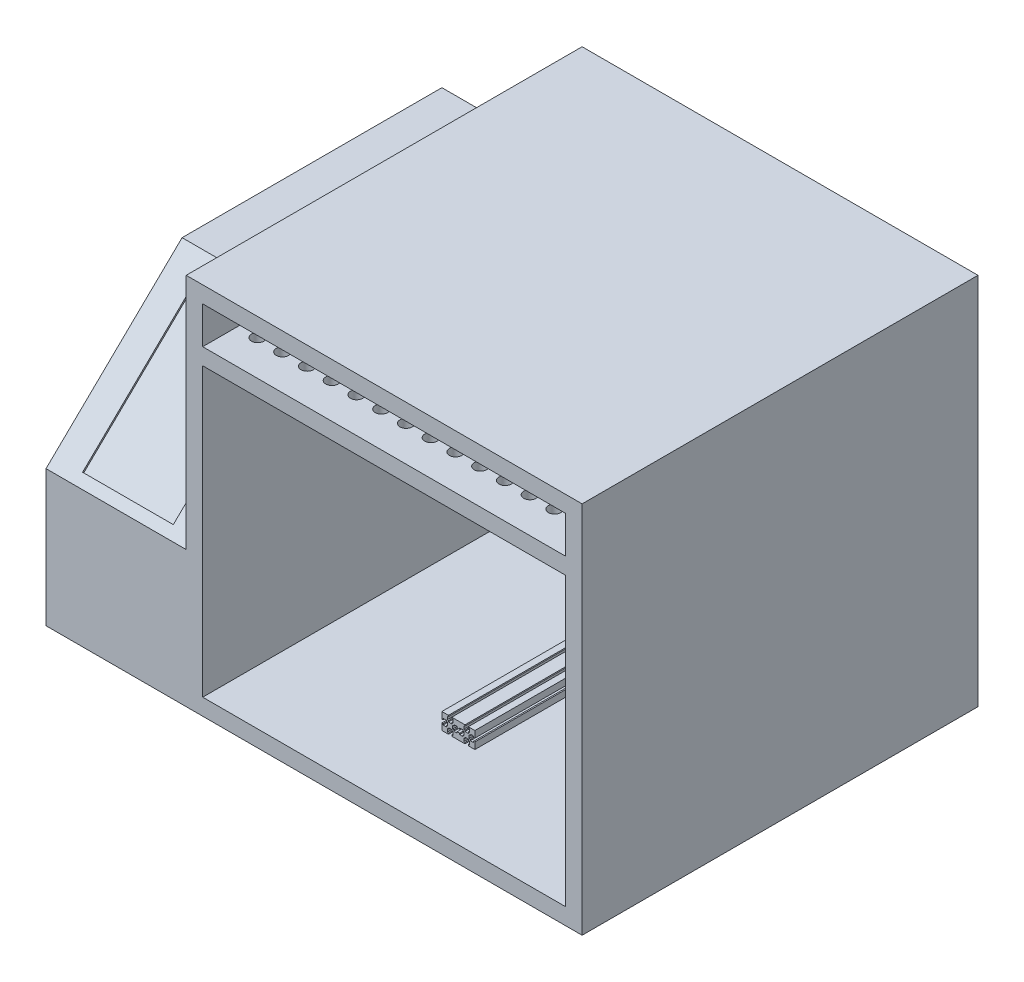
SolidWorks part; units mm, degrees
ref_plane "前视基准面" through (0, 0, 0) normal (0, 0, 1) x (1, 0, 0)
ref_plane "上视基准面" through (0, 0, 0) normal (0, 1, 0) x (1, 0, 0)
ref_plane "右视基准面" through (0, 0, 0) normal (1, 0, 0) x (0, 0, -1)
other "Configuration Table"
sketch "草图1" plane through (0, 0, 0) normal (0, 0, 1) x (1, 0, 0)
  line L0 (170, 20) -> (170, 305)
  line L1 (0, 0) -> (650, 0)
  line L2 (0, 0) -> (0, 325)
  line L3 (170, 453) -> (650, 453)
  line L4 (650, 0) -> (650, 453)
  line L5 (170, 453) -> (170, 325)
  line L6 (190, 388) -> (630, 388)
  line L7 (0, 325) -> (170, 325)
  line L8 (190, 20) -> (190, 368)
  line L9 (630, 20) -> (630, 368)
  line L10 (190, 368) -> (630, 368)
  line L11 (190, 20) -> (630, 20)
  line L12 (170, 20) -> (20, 20)
  line L13 (20, 20) -> (20, 305)
  line L14 (20, 305) -> (170, 305)
  line L15 (190, 388) -> (190, 433)
  line L16 (630, 388) -> (630, 433)
  line L17 (190, 433) -> (630, 433)
  line L18 (170, 325) -> (170, 453)
  line L19 (170, 305) -> (170, 20)
  point P12 (0, 0)
  point P17 (0, 0)
  point P18 (0, 0)
  dimension "D1" = 650
  dimension "D2" = 65
  dimension "D3" = 20
  dimension "D4" = 20
  dimension "D5" = 325
  dimension "D7" = 20
  dimension "D8" = 20
  dimension "D9" = 20
  dimension "D10" = 453
  dimension "D11" = 20
  dimension "D12" = 20
extrude "凸台-拉伸1" add sketch "草图1" along normal blind 480 contours L7 L2 L1 L4 L3 L5 L11 L8 L10 L9 L13 L14 L0 L12 L15 L17 L16 L6 region at (7.9228, 162.5, 0)
sketch "草图2" plane through (0, 0, 0) normal (0, 0, -1) x (-1, 0, 0)
  line L0 (0, 0) -> (-650, 0) construction
  line L1 (-650, 453) -> (-170, 453)
  line L2 (-650, 453) -> (-650, 0)
  line L3 (-650, 0) -> (-170, 0)
  line L4 (-170, 453) -> (-170, 325)
  line L6 (0, 325) -> (-170, 325)
  line L7 (0, 325) -> (0, 0)
  line L8 (0, 0) -> (-170, 0)
extrude "凸台-拉伸2" add sketch "草图2" against normal blind 20
sketch "草图3" plane through (0, 368, 0) normal (0, -1, 0) x (1, 0, 0)
  line L0 (630, 480) -> (630, 0)
  line L1 (0, 0) -> (650, 0) construction
  line L2 (190, 480) -> (190, 0)
  line L3 (0, 480) -> (650, 480) construction
  line L4 (190, 460) -> (650, 460)
  line L5 (650, 480) -> (650, 0) construction
  line L6 (190, 20) -> (650, 20)
  circle A0 centre (213.812, 437.12) radius 7.5
  circle A1 centre (213.812, 407.12) radius 7.5
  circle A2 centre (213.812, 377.12) radius 7.5
  circle A3 centre (213.812, 347.12) radius 7.5
  circle A4 centre (213.812, 317.12) radius 7.5
  circle A5 centre (213.812, 287.12) radius 7.5
  circle A6 centre (213.812, 257.12) radius 7.5
  circle A7 centre (213.812, 227.12) radius 7.5
  circle A8 centre (213.812, 197.12) radius 7.5
  circle A9 centre (213.812, 167.12) radius 7.5
  circle A10 centre (213.812, 137.12) radius 7.5
  circle A11 centre (213.812, 107.12) radius 7.5
  circle A12 centre (213.812, 77.12) radius 7.5
  circle A13 centre (213.812, 47.12) radius 7.5
  circle A14 centre (243.812, 407.12) radius 7.5
  circle A15 centre (243.812, 377.12) radius 7.5
  circle A16 centre (243.812, 347.12) radius 7.5
  circle A17 centre (243.812, 317.12) radius 7.5
  circle A18 centre (243.812, 287.12) radius 7.5
  circle A19 centre (243.812, 257.12) radius 7.5
  circle A20 centre (243.812, 227.12) radius 7.5
  circle A21 centre (243.812, 197.12) radius 7.5
  circle A22 centre (243.812, 167.12) radius 7.5
  circle A23 centre (243.812, 137.12) radius 7.5
  circle A24 centre (243.812, 107.12) radius 7.5
  circle A25 centre (243.812, 77.12) radius 7.5
  circle A26 centre (243.812, 47.12) radius 7.5
  circle A27 centre (273.812, 407.12) radius 7.5
  circle A28 centre (273.812, 377.12) radius 7.5
  circle A29 centre (273.812, 347.12) radius 7.5
  circle A30 centre (273.812, 317.12) radius 7.5
  circle A31 centre (273.812, 287.12) radius 7.5
  circle A32 centre (273.812, 257.12) radius 7.5
  circle A33 centre (273.812, 227.12) radius 7.5
  circle A34 centre (273.812, 197.12) radius 7.5
  circle A35 centre (273.812, 167.12) radius 7.5
  circle A36 centre (273.812, 137.12) radius 7.5
  circle A37 centre (273.812, 107.12) radius 7.5
  circle A38 centre (273.812, 77.12) radius 7.5
  circle A39 centre (273.812, 47.12) radius 7.5
  circle A40 centre (303.812, 407.12) radius 7.5
  circle A41 centre (303.812, 377.12) radius 7.5
  circle A42 centre (303.812, 347.12) radius 7.5
  circle A43 centre (303.812, 317.12) radius 7.5
  circle A44 centre (303.812, 287.12) radius 7.5
  circle A45 centre (303.812, 257.12) radius 7.5
  circle A46 centre (303.812, 227.12) radius 7.5
  circle A47 centre (303.812, 197.12) radius 7.5
  circle A48 centre (303.812, 167.12) radius 7.5
  circle A49 centre (303.812, 137.12) radius 7.5
  circle A50 centre (303.812, 107.12) radius 7.5
  circle A51 centre (303.812, 77.12) radius 7.5
  circle A52 centre (303.812, 47.12) radius 7.5
  circle A53 centre (333.812, 407.12) radius 7.5
  circle A54 centre (333.812, 377.12) radius 7.5
  circle A55 centre (333.812, 347.12) radius 7.5
  circle A56 centre (333.812, 317.12) radius 7.5
  circle A57 centre (333.812, 287.12) radius 7.5
  circle A58 centre (333.812, 257.12) radius 7.5
  circle A59 centre (333.812, 227.12) radius 7.5
  circle A60 centre (333.812, 197.12) radius 7.5
  circle A61 centre (333.812, 167.12) radius 7.5
  circle A62 centre (333.812, 137.12) radius 7.5
  circle A63 centre (333.812, 107.12) radius 7.5
  circle A64 centre (333.812, 77.12) radius 7.5
  circle A65 centre (333.812, 47.12) radius 7.5
  circle A66 centre (363.812, 407.12) radius 7.5
  circle A67 centre (363.812, 377.12) radius 7.5
  circle A68 centre (363.812, 347.12) radius 7.5
  circle A69 centre (363.812, 317.12) radius 7.5
  circle A70 centre (363.812, 287.12) radius 7.5
  circle A71 centre (363.812, 257.12) radius 7.5
  circle A72 centre (363.812, 227.12) radius 7.5
  circle A73 centre (363.812, 197.12) radius 7.5
  circle A74 centre (363.812, 167.12) radius 7.5
  circle A75 centre (363.812, 137.12) radius 7.5
  circle A76 centre (363.812, 107.12) radius 7.5
  circle A77 centre (363.812, 77.12) radius 7.5
  circle A78 centre (363.812, 47.12) radius 7.5
  circle A79 centre (393.812, 407.12) radius 7.5
  circle A80 centre (393.812, 377.12) radius 7.5
  circle A81 centre (393.812, 347.12) radius 7.5
  circle A82 centre (393.812, 317.12) radius 7.5
  circle A83 centre (393.812, 287.12) radius 7.5
  circle A84 centre (393.812, 257.12) radius 7.5
  circle A85 centre (393.812, 227.12) radius 7.5
  circle A86 centre (393.812, 197.12) radius 7.5
  circle A87 centre (393.812, 167.12) radius 7.5
  circle A88 centre (393.812, 137.12) radius 7.5
  circle A89 centre (393.812, 107.12) radius 7.5
  circle A90 centre (393.812, 77.12) radius 7.5
  circle A91 centre (393.812, 47.12) radius 7.5
  circle A92 centre (423.812, 407.12) radius 7.5
  circle A93 centre (423.812, 377.12) radius 7.5
  circle A94 centre (423.812, 347.12) radius 7.5
  circle A95 centre (423.812, 317.12) radius 7.5
  circle A96 centre (423.812, 287.12) radius 7.5
  circle A97 centre (423.812, 257.12) radius 7.5
  circle A98 centre (423.812, 227.12) radius 7.5
  circle A99 centre (423.812, 197.12) radius 7.5
  circle A100 centre (423.812, 167.12) radius 7.5
  circle A101 centre (423.812, 137.12) radius 7.5
  circle A102 centre (423.812, 107.12) radius 7.5
  circle A103 centre (423.812, 77.12) radius 7.5
  circle A104 centre (423.812, 47.12) radius 7.5
  circle A105 centre (453.812, 407.12) radius 7.5
  circle A106 centre (453.812, 377.12) radius 7.5
  circle A107 centre (453.812, 347.12) radius 7.5
  circle A108 centre (453.812, 317.12) radius 7.5
  circle A109 centre (453.812, 287.12) radius 7.5
  circle A110 centre (453.812, 257.12) radius 7.5
  circle A111 centre (453.812, 227.12) radius 7.5
  circle A112 centre (453.812, 197.12) radius 7.5
  circle A113 centre (453.812, 167.12) radius 7.5
  circle A114 centre (453.812, 137.12) radius 7.5
  circle A115 centre (453.812, 107.12) radius 7.5
  circle A116 centre (453.812, 77.12) radius 7.5
  circle A117 centre (453.812, 47.12) radius 7.5
  circle A118 centre (483.812, 407.12) radius 7.5
  circle A119 centre (483.812, 377.12) radius 7.5
  circle A120 centre (483.812, 347.12) radius 7.5
  circle A121 centre (483.812, 317.12) radius 7.5
  circle A122 centre (483.812, 287.12) radius 7.5
  circle A123 centre (483.812, 257.12) radius 7.5
  circle A124 centre (483.812, 227.12) radius 7.5
  circle A125 centre (483.812, 197.12) radius 7.5
  circle A126 centre (483.812, 167.12) radius 7.5
  circle A127 centre (483.812, 137.12) radius 7.5
  circle A128 centre (483.812, 107.12) radius 7.5
  circle A129 centre (483.812, 77.12) radius 7.5
  circle A130 centre (483.812, 47.12) radius 7.5
  circle A131 centre (513.812, 407.12) radius 7.5
  circle A132 centre (513.812, 377.12) radius 7.5
  circle A133 centre (513.812, 347.12) radius 7.5
  circle A134 centre (513.812, 317.12) radius 7.5
  circle A135 centre (513.812, 287.12) radius 7.5
  circle A136 centre (513.812, 257.12) radius 7.5
  circle A137 centre (513.812, 227.12) radius 7.5
  circle A138 centre (513.812, 197.12) radius 7.5
  circle A139 centre (513.812, 167.12) radius 7.5
  circle A140 centre (513.812, 137.12) radius 7.5
  circle A141 centre (513.812, 107.12) radius 7.5
  circle A142 centre (513.812, 77.12) radius 7.5
  circle A143 centre (513.812, 47.12) radius 7.5
  circle A144 centre (543.812, 407.12) radius 7.5
  circle A145 centre (543.812, 377.12) radius 7.5
  circle A146 centre (543.812, 347.12) radius 7.5
  circle A147 centre (543.812, 317.12) radius 7.5
  circle A148 centre (543.812, 287.12) radius 7.5
  circle A149 centre (543.812, 257.12) radius 7.5
  circle A150 centre (543.812, 227.12) radius 7.5
  circle A151 centre (543.812, 197.12) radius 7.5
  circle A152 centre (543.812, 167.12) radius 7.5
  circle A153 centre (543.812, 137.12) radius 7.5
  circle A154 centre (543.812, 107.12) radius 7.5
  circle A155 centre (543.812, 77.12) radius 7.5
  circle A156 centre (543.812, 47.12) radius 7.5
  circle A157 centre (573.812, 407.12) radius 7.5
  circle A158 centre (573.812, 377.12) radius 7.5
  circle A159 centre (573.812, 347.12) radius 7.5
  circle A160 centre (573.812, 317.12) radius 7.5
  circle A161 centre (573.812, 287.12) radius 7.5
  circle A162 centre (573.812, 257.12) radius 7.5
  circle A163 centre (573.812, 227.12) radius 7.5
  circle A164 centre (573.812, 197.12) radius 7.5
  circle A165 centre (573.812, 167.12) radius 7.5
  circle A166 centre (573.812, 137.12) radius 7.5
  circle A167 centre (573.812, 107.12) radius 7.5
  circle A168 centre (573.812, 77.12) radius 7.5
  circle A169 centre (573.812, 47.12) radius 7.5
  circle A170 centre (603.812, 407.12) radius 7.5
  circle A171 centre (603.812, 377.12) radius 7.5
  circle A172 centre (603.812, 347.12) radius 7.5
  circle A173 centre (603.812, 317.12) radius 7.5
  circle A174 centre (603.812, 287.12) radius 7.5
  circle A175 centre (603.812, 257.12) radius 7.5
  circle A176 centre (603.812, 227.12) radius 7.5
  circle A177 centre (603.812, 197.12) radius 7.5
  circle A178 centre (603.812, 167.12) radius 7.5
  circle A179 centre (603.812, 137.12) radius 7.5
  circle A180 centre (603.812, 107.12) radius 7.5
  circle A181 centre (603.812, 77.12) radius 7.5
  circle A182 centre (603.812, 47.12) radius 7.5
  circle A183 centre (243.812, 437.12) radius 7.5
  circle A184 centre (273.812, 437.12) radius 7.5
  circle A185 centre (303.812, 437.12) radius 7.5
  circle A186 centre (333.812, 437.12) radius 7.5
  circle A187 centre (363.812, 437.12) radius 7.5
  circle A188 centre (393.812, 437.12) radius 7.5
  circle A189 centre (423.812, 437.12) radius 7.5
  circle A190 centre (453.812, 437.12) radius 7.5
  circle A191 centre (483.812, 437.12) radius 7.5
  circle A192 centre (513.812, 437.12) radius 7.5
  circle A193 centre (543.812, 437.12) radius 7.5
  circle A194 centre (573.812, 437.12) radius 7.5
  circle A195 centre (603.812, 437.12) radius 7.5
  point P16 (213.812, 437.12)
  dimension "D7" = 15
  dimension "D1" = 20
  dimension "D2" = 440
  dimension "D3" = 20
  dimension "D4" = 20
  dimension "D5" = 23.812
  dimension "D6" = 22.88
  dimension "D8" = 14
  dimension "D9" = 14
extrude "切除-拉伸7" cut sketch "草图3" against normal blind 20 contours A4 | A5 | A6 | A7 | A8 | A11 | A16 | A17 | A15 | A14 | A183 | A184 | A27 | A28 | A29 | A30 | A31 | A18 | A19 | A20 | A21 | A34 | A33 | A22 | A23 | A36 | A24 | A9 | A10 | A12 | A13 | A26 | A25 | A37 | A35 | A38 | A39 | A185 | A40 | A41 | A42 | A43 | A44 | A45 | A47 | A48 | A49 | A50 | A51 | A52 | A53 | A54 | A55 | A56 | A57 | A58 | A60 | A61 | A62 | A63 | A65 | A78 | A77 | A76 | A74 | A73 | A72 | A71 | A70 | A68 | A67 | A66 | A187 | A0 | A1 | A2 | A3 | A32 | A46 | A186 | A59 | A64 | A75 | A69 region at (213.812, 368, 317.12) region at (213.812, 368, 287.12) region at (213.812, 368, 257.12) region at (213.812, 368, 227.12) region at (213.812, 368, 197.12) region at (213.812, 368, 167.12) region at (213.812, 368, 137.12) region at (213.812, 368, 107.12) region at (213.812, 368, 77.12) region at (213.812, 368, 47.12) region at (243.812, 368, 407.12) region at (243.812, 368, 377.12) region at (243.812, 368, 347.12) region at (243.812, 368, 317.12) region at (243.812, 368, 287.12) region at (243.812, 368, 257.12) region at (243.812, 368, 227.12) region at (243.812, 368, 197.12) region at (243.812, 368, 167.12) region at (243.812, 368, 137.12) region at (243.812, 368, 107.12) region at (243.812, 368, 77.12) region at (243.812, 368, 47.12) region at (273.812, 368, 407.12) region at (273.812, 368, 377.12) region at (273.812, 368, 347.12) region at (273.812, 368, 317.12) region at (273.812, 368, 287.12) region at (273.812, 368, 227.12) region at (273.812, 368, 197.12) region at (273.812, 368, 167.12) region at (273.812, 368, 137.12) region at (273.812, 368, 107.12) region at (273.812, 368, 77.12) region at (273.812, 368, 47.12) region at (303.812, 368, 407.12) region at (303.812, 368, 377.12) region at (303.812, 368, 347.12) region at (303.812, 368, 317.12) region at (303.812, 368, 287.12) region at (303.812, 368, 257.12) region at (303.812, 368, 197.12) region at (303.812, 368, 167.12) region at (303.812, 368, 137.12) region at (303.812, 368, 107.12) region at (303.812, 368, 77.12) region at (303.812, 368, 47.12) region at (333.812, 368, 407.12) region at (333.812, 368, 377.12) region at (333.812, 368, 347.12) region at (333.812, 368, 317.12) region at (333.812, 368, 287.12) region at (333.812, 368, 257.12) region at (333.812, 368, 197.12) region at (333.812, 368, 167.12) region at (333.812, 368, 137.12) region at (333.812, 368, 107.12) region at (333.812, 368, 47.12) region at (363.812, 368, 407.12) region at (363.812, 368, 377.12)
extrude "切除-拉伸8" cut sketch "草图3<8>" against normal blind 20 contours A188 | A79 | A80 | A81 | A82 | A83 | A84 | A85 | A86 | A88 | A89 | A90 | A91 | A104 | A103 | A102 | A99 | A98 | A97 | A96 | A94 | A93 | A92 | A189 | A190 | A105 | A106 | A108 | A109 | A111 | A112 | A113 | A114 | A117 | A107 | A87 | A101 | A100 | A95 | A110 | A115 | A116 region at (393.812, 368, 407.12) region at (393.812, 368, 377.12) region at (393.812, 368, 347.12) region at (393.812, 368, 317.12) region at (393.812, 368, 287.12) region at (393.812, 368, 257.12) region at (393.812, 368, 227.12) region at (393.812, 368, 197.12) region at (393.812, 368, 137.12) region at (393.812, 368, 107.12) region at (393.812, 368, 77.12) region at (393.812, 368, 47.12) region at (423.812, 368, 407.12) region at (423.812, 368, 377.12) region at (423.812, 368, 347.12) region at (423.812, 368, 287.12) region at (423.812, 368, 257.12) region at (423.812, 368, 227.12) region at (423.812, 368, 197.12) region at (423.812, 368, 107.12) region at (423.812, 368, 77.12) region at (423.812, 368, 47.12) region at (453.812, 368, 407.12) region at (453.812, 368, 377.12) region at (453.812, 368, 347.12) region at (453.812, 368, 317.12) region at (453.812, 368, 287.12) region at (453.812, 368, 227.12) region at (453.812, 368, 197.12) region at (453.812, 368, 167.12) region at (453.812, 368, 137.12) region at (453.812, 368, 47.12) region at (393.812, 368, 437.12) region at (423.812, 368, 437.12) region at (453.812, 368, 437.12)
sketch "草图3<8>" plane through (0, 368, 0) normal (0, -1, 0) x (1, 0, 0) same geometry as "草图3"
extrude "切除-拉伸9" cut sketch "草图3<9>" against normal blind 20 contours A191 | A119 | A125 | A126 | A127 | A128 | A130 | A118 | A120 | A121 | A122 | A123 | A124 | A129 region at (483.812, 368, 377.12) region at (483.812, 368, 197.12) region at (483.812, 368, 167.12) region at (483.812, 368, 137.12) region at (483.812, 368, 107.12) region at (483.812, 368, 47.12) region at (483.812, 368, 437.12)
sketch "草图3<9>" plane through (0, 368, 0) normal (0, -1, 0) x (1, 0, 0) same geometry as "草图3"
extrude "切除-拉伸10" cut sketch "草图3<10>" against normal blind 20 contours A193 | A194 | A195 | A170 | A144 | A132 | A134 | A135 | A136 | A140 | A141 | A156 | A155 | A154 | A153 | A152 | A151 | A149 | A145 | A158 | A171 | A159 | A172 | A160 | A173 | A192 | A157 | A131 | A133 | A137 | A138 | A139 | A142 | A143 | A150 | A148 | A147 | A146 region at (513.812, 368, 377.12) region at (513.812, 368, 317.12) region at (513.812, 368, 287.12) region at (513.812, 368, 257.12) region at (513.812, 368, 137.12) region at (513.812, 368, 107.12) region at (543.812, 368, 407.12) region at (543.812, 368, 377.12) region at (543.812, 368, 257.12) region at (543.812, 368, 197.12) region at (543.812, 368, 167.12) region at (543.812, 368, 137.12) region at (543.812, 368, 107.12) region at (543.812, 368, 77.12) region at (543.812, 368, 47.12) region at (573.812, 368, 377.12) region at (573.812, 368, 347.12) region at (573.812, 368, 317.12) region at (603.812, 368, 407.12) region at (603.812, 368, 377.12) region at (603.812, 368, 347.12) region at (603.812, 368, 317.12) region at (543.812, 368, 437.12) region at (573.812, 368, 437.12) region at (603.812, 368, 437.12)
sketch "草图3<10>" plane through (0, 368, 0) normal (0, -1, 0) x (1, 0, 0) same geometry as "草图3"
extrude "切除-拉伸11" cut sketch "草图3<11>" against normal blind 20 contours A161 | A162 | A163 | A165 | A166 | A178 | A177 | A175 | A176 | A174 | A167 | A168 | A169 | A182 | A181 | A180 | A164 | A179 region at (573.812, 368, 287.12) region at (573.812, 368, 257.12) region at (573.812, 368, 227.12) region at (573.812, 368, 167.12) region at (573.812, 368, 137.12) region at (573.812, 368, 107.12) region at (573.812, 368, 77.12) region at (573.812, 368, 47.12) region at (603.812, 368, 287.12) region at (603.812, 368, 257.12) region at (603.812, 368, 227.12) region at (603.812, 368, 197.12) region at (603.812, 368, 167.12) region at (603.812, 368, 107.12) region at (603.812, 368, 77.12) region at (603.812, 368, 47.12)
sketch "草图3<11>" plane through (0, 368, 0) normal (0, -1, 0) x (1, 0, 0) same geometry as "草图3"
sketch "草图10" plane through (0, 20, 0) normal (0, 1, 0) x (1, 0, 0)
  line L2 (170, -480) -> (650, -480) construction
  line L7 (370, -20) -> (370, -370)
  line L8 (410, -20) -> (410, -370)
  line L9 (370, -370) -> (410, -370)
  line L10 (370, -20) -> (410, -20)
  line L11 (240, -110) -> (280, -110)
  line L12 (240, -110) -> (240, -130)
  line L13 (240, -130) -> (280, -130)
  line L14 (280, -110) -> (280, -130)
  point P0 (0, 0)
  point P8 (170, 0)
  point P9 (650, 0)
  point P22 (190, -20)
  dimension "D4" = 180
  dimension "D5" = 40
  dimension "D6" = 350
  dimension "D7" = 40
  dimension "D8" = 20
  dimension "D10" = 350
extrude "凸台-拉伸4" add sketch "草图10" along normal blind 20 contours L7 L9 L8 L10
sketch "草图11" plane through (0, 20, 0) normal (0, 1, 0) x (1, 0, 0)
  line L0 (190, 0) -> (190, -480)
  line L1 (170, 0) -> (650, 0) construction
  line L2 (170, -480) -> (650, -480) construction
  line L3 (170, -20) -> (650, -20)
  line L4 (170, -480) -> (170, 0) construction
  line L5 (650, -480) -> (650, 0) construction
  line L6 (630, 0) -> (630, -480)
  line L8 (240, -110) -> (280, -110)
  line L9 (240, -110) -> (240, -130)
  line L10 (240, -130) -> (280, -130)
  line L11 (280, -110) -> (280, -130)
  point P22 (249.8104, -197.4415)
  point P23 (231.2394, -178.8705)
  point P24 (245.2809, -197.4415)
  dimension "D1" = 20
  dimension "D2" = 20
  dimension "D3" = 20
  dimension "D4" = 20
  dimension "D5" = 40
  dimension "D6" = 50
  dimension "D7" = 350
extrude "凸台-拉伸6" add sketch "草图11" along normal blind 348 contours L11 L8 L9 L10 region at (260, 20, 120)
sketch "草图12" plane through (0, 0, 0) normal (-1, 0, 0) x (0, 0, 1)
  line L0 (315, 325) -> (480, 165)
  line L1 (480, 325) -> (0, 325) construction
  line L2 (480, 0) -> (480, 325) construction
  line L3 (315, 325) -> (480, 325)
  line L4 (480, 325) -> (480, 165)
  dimension "D1" = 165
  dimension "D2" = 160
extrude "切除-拉伸12" cut sketch "草图12" against normal blind 170
sketch "草图13" plane through (0, 0, 480) normal (0, 0, 1) x (1, 0, 0)
  line L0 (0, 0) -> (650, 0) construction
  line L1 (0, 165) -> (190, 165)
  line L2 (0, 165) -> (0, 0)
  line L3 (0, 0) -> (190, 0)
  line L4 (190, 165) -> (190, 0)
  dimension "D1" = 190
extrude "凸台-拉伸7" add sketch "草图13" against normal blind 20
sketch "草图14" plane through (0, 324.9243, 315.0781) normal (0, 0.7179, 0.6961) x (1, 0, 0)
  line L1 (0, 0) -> (170, 0)
  line L2 (0, 0) -> (0, -229.7281)
  line L3 (0, -229.7281) -> (170, -229.7281)
  line L4 (170, 0) -> (170, -229.7281)
extrude "凸台-拉伸8" add sketch "草图14" against normal blind 15
sketch "草图15" plane through (0, 324.9243, 315.0781) normal (0, 0.7179, 0.6961) x (1, 0, 0)
  line L0 (0, 0.1088) -> (0, -229.7281) construction
  line L1 (35, -19.8912) -> (145, -19.8912)
  line L2 (35, -19.8912) -> (35, -216.7281)
  line L3 (35, -216.7281) -> (145, -216.7281)
  line L4 (145, -19.8912) -> (145, -216.7281)
  line L5 (170, -29.2381) -> (170, 315.3541) construction
  line L6 (0, -229.7281) -> (170, -229.7281) construction
  line L7 (170, 0.1088) -> (0, 0.1088) construction
  point P12 (85, 0.1088)
  dimension "D1" = 35
  dimension "D2" = 25
  dimension "D3" = 13
  dimension "D4" = 20
extrude "切除-拉伸13" cut sketch "草图15" against normal blind 2 contours L2 L1 L4 L3
sketch "草图16" plane through (0, 0, 130) normal (0, 0, 1) x (1, 0, 0)
  line L0 (190, 368) -> (190, 20) construction
  line L1 (190, 310.431) -> (630, 310.431)
  line L2 (190, 310.431) -> (190, 290.431)
  line L3 (190, 290.431) -> (630, 290.431)
  line L4 (630, 310.431) -> (630, 290.431)
  line L5 (630, 20) -> (630, 368) construction
  line L8 (190, 322.5085) -> (190, 279.5085)
  line L10 (240, 350.431) -> (240, 250.431)
  line L11 (240, 368) -> (240, 20) construction
  line L12 (190, 322.5085) -> (240, 350.431)
  line L13 (190, 322.5085) -> (233, 322.5085)
  line L14 (190, 322.5085) -> (190, 279.5085)
  line L15 (190, 279.5085) -> (233, 279.5085)
  line L16 (233, 322.5085) -> (233, 279.5085)
  line L17 (190, 279.5085) -> (240, 250.431)
  line M2 (280, 20) -> (280, 368)
  line M8 (240, 368) -> (240, 20)
  dimension "D1" = 100
  dimension "D2" = 20
  dimension "D4" = 43
  dimension "D5" = 43
extrude "凸台-拉伸12" add sketch "草图16" along normal blind 20 contours L4 L1 L3 M2 | L3 L1 M8 M2 | L16 L1 L2 L3 | L1 L16 L3 M8 | L16 L13 L8 L1 | L16 L3 L8 L15 region at (211.5, 316.4698, 130) region at (211.5, 300.431, 130) region at (236.5, 300.431, 130) region at (211.5, 284.9698, 130) region at (260, 300.431, 130) region at (455, 300.431, 130)
sketch "草图17" plane through (0, 0, 150) normal (0, 0, 1) x (1, 0, 0)
  line L0 (190, 20) -> (190, 368) construction
  line L1 (190, 322.5085) -> (233, 322.5085)
  line L2 (190, 322.5085) -> (190, 279.5085)
  line L3 (190, 279.5085) -> (233, 279.5085)
  line L4 (233, 322.5085) -> (233, 279.5085)
  line L5 (190, 368) -> (190, 20) construction
  line L6 (233, 290.431) -> (233, 279.5085) construction
extrude "凸台-拉伸13" add sketch "草图17" along normal blind 20
sketch "草图18" plane through (0, 20, 0) normal (0, 1, 0) x (1, 0, 0)
  line L0 (170, -20) -> (650, -20)
  line L1 (170, -315) -> (170, 0) construction
  line L2 (650, -480) -> (650, 0) construction
  line L3 (370, 0) -> (370, -480)
  line L4 (170, 0) -> (650, 0) construction
  line L5 (170, -480) -> (650, -480) construction
  line L6 (370, -480) -> (410, -480)
  line L7 (410, -480) -> (410, 0)
  line L8 (410, 0) -> (370, 0)
  line L10 (330, -20) -> (453.0047, -20)
  line L11 (330, -20) -> (330, -61.6255)
  line L12 (330, -61.6255) -> (453.0047, -61.6255)
  line L13 (453.0047, -20) -> (453.0047, -61.6255)
  point P12 (370, -20)
  line M9 (370, -20) -> (190, -20)
  dimension "D1" = 20
  dimension "D2" = 40
  dimension "D3" = 123.0047
  dimension "D4" = 40
extrude "凸台-拉伸14" add sketch "草图18" along normal blind 40 contours L11 L12 L3 M9 region at (350, 20, 40.8128)
sketch "草图19" plane through (0, 20, 0) normal (0, 1, 0) x (1, 0, 0)
  line L1 (240.1404, -109.9682) -> (280.1404, -109.9682)
  line L2 (240.1404, -109.9682) -> (240.1404, -69.9682)
  line L3 (240.1404, -69.9682) -> (280.1404, -69.9682)
  line L4 (280.1404, -109.9682) -> (280.1404, -69.9682)
  point P6 (216.7887, -101.5043)
  point P7 (242.8426, -112.3229)
  point P8 (198.8997, -102.796)
  dimension "D1" = 40
extrude "凸台-拉伸15" add sketch "草图19" along normal blind 40
sketch "草图20" plane through (0, 0, 150) normal (0, 0, 1) x (1, 0, 0)
  line L0 (416.4432, 260.2447) -> (446.4432, 260.2447)
  line L1 (400.6426, 325.2447) -> (460.6426, 325.2447)
  line L2 (400.6426, 325.2447) -> (400.6426, 290.431)
  line L3 (416.4432, 260.2447) -> (446.4432, 260.2447)
  line L4 (460.6426, 325.2447) -> (460.6426, 290.431)
  line L5 (233, 290.431) -> (630, 290.431) construction
  line L6 (400.6426, 290.431) -> (416.4432, 260.2447)
  line L7 (446.4432, 260.2447) -> (460.6426, 290.431)
  point P6 (400.6426, 290.431)
  point P7 (460.6426, 290.431)
  line M7 (630, 310.431) -> (233, 310.431)
  line M9 (233, 290.431) -> (630, 290.431)
  dimension "D1" = 60
  dimension "D3" = 30
extrude "凸台-拉伸16" add sketch "草图20" along normal blind 2 contours L4 L1 L2 M7 | L4 L2 M7 M9 | L0 L7 L6 M9 region at (430.9984, 277.0149, 150) region at (430.6426, 300.431, 150) region at (430.6426, 317.8379, 150)
sketch "草图22" plane through (0, 60, 0) normal (0, 1, 0) x (1, 0, 0)
  circle A0 centre (259.3223, -90.3002) radius 4
  dimension "D1" = 8
extrude "凸台-拉伸17" add sketch "草图22" along normal blind 308
sketch "草图23" plane through (0, 60, 0) normal (0, 1, 0) x (1, 0, 0)
  circle A0 centre (259.3321, -90.4081) radius 12.5
  dimension "D1" = 25
extrude "凸台-拉伸18" add sketch "草图23" along normal blind 18.4969 contours A0
sketch "草图24" plane through (0, 0, 370) normal (0, 0, 1) x (1, 0, 0)
  line L0 (390, 40) -> (390, 20)
  line L1 (370, 40) -> (410, 40) construction
  line L2 (370, 20) -> (410, 20) construction
  line L3 (398, 40) -> (398, 38.5)
  line L4 (370, 40) -> (410, 40) construction
  line L5 (398, 38.5) -> (396.5, 38.5)
  line L6 (396.5, 38.5) -> (396.5, 34.5)
  line L7 (396.5, 34.5) -> (398, 34.5)
  line L8 (398, 34.5) -> (398, 33)
  line L9 (398, 33) -> (402, 33)
  line L10 (402, 33) -> (402, 34.5)
  line L11 (402, 34.5) -> (403.5, 34.5)
  line L12 (403.5, 34.5) -> (403.5, 38.5)
  line L13 (403.5, 38.5) -> (402, 38.5)
  line L14 (402, 38.5) -> (402, 40)
  line L15 (402, 40) -> (398, 40)
  line L16 (390, 40) -> (410, 20)
  line L17 (190, 20) -> (630, 20) construction
  line L18 (410, 20) -> (400, 30)
  line L19 (410, 28) -> (410, 32)
  line L20 (410, 32) -> (408.5, 32)
  line L21 (408.5, 32) -> (408.5, 33.5)
  line L22 (408.5, 33.5) -> (404.5, 33.5)
  line L23 (404.5, 33.5) -> (404.5, 32)
  line L24 (404.5, 32) -> (403, 32)
  line L25 (403, 32) -> (403, 28)
  line L26 (403, 28) -> (404.5, 28)
  line L27 (404.5, 28) -> (404.5, 26.5)
  line L28 (404.5, 26.5) -> (408.5, 26.5)
  line L29 (408.5, 26.5) -> (408.5, 28)
  line L30 (408.5, 28) -> (410, 28)
  line L31 (398, 20) -> (402, 20)
  line L32 (402, 20) -> (402, 21.5)
  line L33 (402, 21.5) -> (403.5, 21.5)
  line L34 (403.5, 21.5) -> (403.5, 25.5)
  line L35 (403.5, 25.5) -> (402, 25.5)
  line L36 (402, 25.5) -> (402, 27)
  line L37 (402, 27) -> (398, 27)
  line L38 (398, 27) -> (398, 25.5)
  line L39 (398, 25.5) -> (396.5, 25.5)
  line L40 (396.5, 25.5) -> (396.5, 21.5)
  line L41 (396.5, 21.5) -> (398, 21.5)
  line L42 (398, 21.5) -> (398, 20)
  line L43 (390, 32) -> (390, 28)
  line L44 (390, 28) -> (391.5, 28)
  line L45 (391.5, 28) -> (391.5, 26.5)
  line L46 (391.5, 26.5) -> (395.5, 26.5)
  line L47 (395.5, 26.5) -> (395.5, 28)
  line L48 (395.5, 28) -> (397, 28)
  line L49 (397, 28) -> (397, 32)
  line L50 (397, 32) -> (395.5, 32)
  line L51 (395.5, 32) -> (395.5, 33.5)
  line L52 (395.5, 33.5) -> (391.5, 33.5)
  line L53 (391.5, 33.5) -> (391.5, 32)
  line L54 (391.5, 32) -> (390, 32)
  line L55 (370, 32) -> (370, 28)
  line L56 (370, 28) -> (371.5, 28)
  line L57 (371.5, 28) -> (371.5, 26.5)
  line L58 (371.5, 26.5) -> (375.5, 26.5)
  line L59 (375.5, 26.5) -> (375.5, 28)
  line L60 (375.5, 28) -> (377, 28)
  line L61 (377, 28) -> (377, 32)
  line L62 (377, 32) -> (375.5, 32)
  line L63 (375.5, 32) -> (375.5, 33.5)
  line L64 (375.5, 33.5) -> (371.5, 33.5)
  line L65 (371.5, 33.5) -> (371.5, 32)
  line L66 (371.5, 32) -> (370, 32)
  line L67 (378, 20) -> (382, 20)
  line L68 (382, 20) -> (382, 21.5)
  line L69 (382, 21.5) -> (383.5, 21.5)
  line L70 (383.5, 21.5) -> (383.5, 25.5)
  line L71 (383.5, 25.5) -> (382, 25.5)
  line L72 (382, 25.5) -> (382, 27)
  line L73 (382, 27) -> (378, 27)
  line L74 (378, 27) -> (378, 25.5)
  line L75 (378, 25.5) -> (376.5, 25.5)
  line L76 (376.5, 25.5) -> (376.5, 21.5)
  line L77 (376.5, 21.5) -> (378, 21.5)
  line L78 (378, 21.5) -> (378, 20)
  line L79 (382, 40) -> (378, 40)
  line L80 (378, 40) -> (378, 38.5)
  line L81 (378, 38.5) -> (376.5, 38.5)
  line L82 (376.5, 38.5) -> (376.5, 34.5)
  line L83 (376.5, 34.5) -> (378, 34.5)
  line L84 (378, 34.5) -> (378, 33)
  line L85 (378, 33) -> (382, 33)
  line L86 (382, 33) -> (382, 34.5)
  line L87 (382, 34.5) -> (383.5, 34.5)
  line L88 (383.5, 34.5) -> (383.5, 38.5)
  line L89 (383.5, 38.5) -> (382, 38.5)
  line L90 (382, 38.5) -> (382, 40)
  line L91 (390, 28) -> (390, 32)
  line L92 (390, 32) -> (388.5, 32)
  line L93 (388.5, 32) -> (388.5, 33.5)
  line L94 (388.5, 33.5) -> (384.5, 33.5)
  line L95 (384.5, 33.5) -> (384.5, 32)
  line L96 (384.5, 32) -> (383, 32)
  line L97 (383, 32) -> (383, 28)
  line L98 (383, 28) -> (384.5, 28)
  line L99 (384.5, 28) -> (384.5, 26.5)
  line L100 (384.5, 26.5) -> (388.5, 26.5)
  line L101 (388.5, 26.5) -> (388.5, 28)
  line L102 (388.5, 28) -> (390, 28)
  point P63 (400, 30)
  line M61 (370, 20) -> (410, 20)
  line M62 (410, 20) -> (410, 40)
  line M63 (410, 40) -> (370, 40)
  line M64 (370, 40) -> (370, 20)
  dimension "D1" = 4
  dimension "D2" = 4
  dimension "D3" = 1.5
  dimension "D4" = 8
  dimension "D5" = 1.5
  dimension "D6" = 1.5
  dimension "D7" = 1.5
  dimension "D9" = 2
  dimension "D8" = 4
extrude "切除-拉伸14" cut sketch "草图24" against normal blind 350 contours L65 L66 L56 L57 L58 L59 L60 L61 L62 L63 L64 M64 | L89 L90 L80 L81 L82 L83 L84 L85 L86 L87 L88 M63 | L77 L78 L68 L69 L70 L71 L72 L73 L74 L75 L76 M61 | L101 L102 L0 L92 L93 L94 L95 L96 L97 L98 L99 L100 | L53 L54 L0 L44 L45 L46 L47 L48 L49 L50 L51 L52 | L41 L42 L32 L33 L34 L35 L36 L37 L38 L39 L40 M61 | L13 L14 L3 L5 L6 L7 L8 L9 L10 L11 L12 M63 | L29 L30 L20 L21 L22 L23 L24 L25 L26 L27 L28 M62 region at (393.5, 30, 370) region at (386.5, 30, 370) region at (400, 36.5, 370) region at (380, 36.5, 370) region at (400, 23.5, 370) region at (406.5, 30, 370) region at (380, 23.5, 370) region at (373.5, 30, 370)
sketch "草图26" plane through (630, 0, 0) normal (-1, 0, 0) x (0, 0, 1)
  line L0 (144.2161, 310.431) -> (144.2161, 308.931)
  line L1 (144.2161, 290.431) -> (140.2161, 290.431)
  line L2 (152.2161, 298.431) -> (152.2161, 302.431)
  line L3 (144.2161, 310.431) -> (140.2161, 310.431)
  line L4 (132.2161, 298.431) -> (132.2161, 302.431)
  line L5 (144.2161, 308.931) -> (145.7161, 308.931)
  line L6 (145.7161, 308.931) -> (145.7161, 304.931)
  line L7 (145.7161, 304.931) -> (144.2161, 304.931)
  line L8 (144.2161, 304.931) -> (144.2161, 303.431)
  line L9 (144.2161, 303.431) -> (140.2161, 303.431)
  line L10 (140.2161, 303.431) -> (140.2161, 304.931)
  line L11 (140.2161, 304.931) -> (138.7161, 304.931)
  line L12 (138.7161, 304.931) -> (138.7161, 308.931)
  line L13 (138.7161, 308.931) -> (140.2161, 308.931)
  line L14 (140.2161, 308.931) -> (140.2161, 310.431)
  line L18 (152.2161, 298.431) -> (150.7161, 298.431)
  line L19 (150.7161, 298.431) -> (150.7161, 296.931)
  line L20 (150.7161, 296.931) -> (146.7161, 296.931)
  line L21 (146.7161, 296.931) -> (146.7161, 298.431)
  line L22 (146.7161, 298.431) -> (145.2161, 298.431)
  line L23 (145.2161, 298.431) -> (145.2161, 302.431)
  line L24 (145.2161, 302.431) -> (146.7161, 302.431)
  line L25 (146.7161, 302.431) -> (146.7161, 303.931)
  line L26 (146.7161, 303.931) -> (150.7161, 303.931)
  line L27 (150.7161, 303.931) -> (150.7161, 302.431)
  line L28 (150.7161, 302.431) -> (152.2161, 302.431)
  line L30 (140.2161, 290.431) -> (140.2161, 291.931)
  line L31 (140.2161, 291.931) -> (138.7161, 291.931)
  line L32 (138.7161, 291.931) -> (138.7161, 295.931)
  line L33 (138.7161, 295.931) -> (140.2161, 295.931)
  line L34 (140.2161, 295.931) -> (140.2161, 297.431)
  line L35 (140.2161, 297.431) -> (144.2161, 297.431)
  line L36 (144.2161, 297.431) -> (144.2161, 295.931)
  line L37 (144.2161, 295.931) -> (145.7161, 295.931)
  line L38 (145.7161, 295.931) -> (145.7161, 291.931)
  line L39 (145.7161, 291.931) -> (144.2161, 291.931)
  line L40 (144.2161, 291.931) -> (144.2161, 290.431)
  line L42 (132.2161, 302.431) -> (133.7161, 302.431)
  line L43 (133.7161, 302.431) -> (133.7161, 303.931)
  line L44 (133.7161, 303.931) -> (137.7161, 303.931)
  line L45 (137.7161, 303.931) -> (137.7161, 302.431)
  line L46 (137.7161, 302.431) -> (139.2161, 302.431)
  line L47 (139.2161, 302.431) -> (139.2161, 298.431)
  line L48 (139.2161, 298.431) -> (137.7161, 298.431)
  line L49 (137.7161, 298.431) -> (137.7161, 296.931)
  line L50 (137.7161, 296.931) -> (133.7161, 296.931)
  line L51 (133.7161, 296.931) -> (133.7161, 298.431)
  line L52 (133.7161, 298.431) -> (132.2161, 298.431)
  point P17 (142.2161, 300.431)
  point P57 (142.2161, 300.431)
  dimension "D3" = 4
  dimension "D4" = 1.5
  dimension "D5" = 4
  dimension "D6" = 1.5
  dimension "D7" = 1.5
  dimension "D8" = 1.5
  dimension "D10" = 4
extrude "切除-拉伸16" cut sketch "草图26" along normal blind 395 contours L3 L14 L13 L12 L11 L10 L9 L8 L7 L6 L5 L0 | L4 L42 L43 L44 L45 L46 L47 L48 L49 L50 L51 L52 | L1 L30 L31 L32 L33 L34 L35 L36 L37 L38 L39 L40 | L2 L28 L27 L26 L25 L24 L23 L22 L21 L20 L19 L18
sketch "草图27" plane through (0, 0, 152) normal (0, 0, 1) x (1, 0, 0)
  line L0 (426.2382, 253.5183) -> (430.9821, 249.8637)
  line L1 (426.2382, 269.9638) -> (435.726, 269.9638)
  line L2 (426.2382, 269.9638) -> (426.2382, 253.5183)
  line L4 (435.726, 269.9638) -> (435.726, 253.5183)
  line L5 (430.9821, 249.8637) -> (435.726, 253.5183)
extrude "凸台-拉伸19" add sketch "草图27" along normal blind 10
sketch "草图28" plane through (0, 269.9638, 0) normal (0, 1, 0) x (1, 0, 0)
  line L0 (426.2648, -151.9715) -> (435.7526, -161.9715)
  line L1 (426.2648, -161.9715) -> (435.7526, -161.9715)
  line L2 (426.2648, -161.9715) -> (426.2648, -151.9715)
  line L3 (426.2648, -151.9715) -> (435.7526, -151.9715)
  line L4 (435.7526, -161.9715) -> (435.7526, -151.9715)
  circle A0 centre (431.0087, -156.9715) radius 2.5
  dimension "D3" = 5
  dimension "D1" = 9.4878
  dimension "D2" = 10
sketch "草图29" plane through (650, 0, 0) normal (1, 0, 0) x (0, 0, -1)
  line L0 (-156.9715, 269.9638) -> (-156.9715, 391.0425)
  line L1 (-161.9715, 269.9638) -> (-151.9715, 269.9638) construction
  line L2 (-141.9715, 406.0425) -> (0, 406.0425)
  line L3 (0, 0) -> (0, 453) construction
  arc A0 (-156.9715, 391.0425) -> (-141.9715, 406.0425) centre (-141.9715, 391.0425) cw
  dimension "D1" = 15
sweep "扫描1" add profiles "草图28" path "草图29"
ref_plane "基准面1" through (280, 20, 130) normal (1, 0, 0) x (0, 0, -1)
sketch "草图32" plane through (0, 20, 0) normal (0, 1, 0) x (1, 0, 0)
  line L1 (248.0177, -129.962) -> (252.0177, -129.962)
  line L2 (240.0177, -121.962) -> (240.0177, -117.962)
  line L3 (248.0177, -109.962) -> (252.0177, -109.962)
  line L4 (280.0177, -121.962) -> (280.0177, -117.962)
  line L5 (268.0177, -109.962) -> (268.0177, -111.462)
  line L6 (268.0177, -111.462) -> (266.5177, -111.462)
  line L7 (266.5177, -111.462) -> (266.5177, -115.462)
  line L8 (266.5177, -115.462) -> (268.0177, -115.462)
  line L9 (268.0177, -115.462) -> (268.0177, -116.962)
  line L10 (268.0177, -116.962) -> (272.0177, -116.962)
  line L11 (272.0177, -116.962) -> (272.0177, -115.462)
  line L12 (272.0177, -115.462) -> (273.5177, -115.462)
  line L13 (273.5177, -115.462) -> (273.5177, -111.462)
  line L14 (273.5177, -111.462) -> (272.0177, -111.462)
  line L15 (272.0177, -111.462) -> (272.0177, -109.962)
  line L17 (280.0177, -117.962) -> (278.5177, -117.962)
  line L18 (278.5177, -117.962) -> (278.5177, -116.462)
  line L19 (278.5177, -116.462) -> (274.5177, -116.462)
  line L20 (274.5177, -116.462) -> (274.5177, -117.962)
  line L21 (274.5177, -117.962) -> (273.0177, -117.962)
  line L22 (273.0177, -117.962) -> (273.0177, -121.962)
  line L23 (273.0177, -121.962) -> (274.5177, -121.962)
  line L24 (274.5177, -121.962) -> (274.5177, -123.462)
  line L25 (274.5177, -123.462) -> (278.5177, -123.462)
  line L26 (278.5177, -123.462) -> (278.5177, -121.962)
  line L27 (278.5177, -121.962) -> (280.0177, -121.962)
  line L29 (272.0177, -129.962) -> (272.0177, -128.462)
  line L30 (272.0177, -128.462) -> (273.5177, -128.462)
  line L31 (273.5177, -128.462) -> (273.5177, -124.462)
  line L32 (273.5177, -124.462) -> (272.0177, -124.462)
  line L33 (272.0177, -124.462) -> (272.0177, -122.962)
  line L34 (272.0177, -122.962) -> (268.0177, -122.962)
  line L35 (268.0177, -122.962) -> (268.0177, -124.462)
  line L36 (268.0177, -124.462) -> (266.5177, -124.462)
  line L37 (266.5177, -124.462) -> (266.5177, -128.462)
  line L38 (266.5177, -128.462) -> (268.0177, -128.462)
  line L39 (268.0177, -128.462) -> (268.0177, -129.962)
  line L41 (260.0177, -121.962) -> (261.5177, -121.962)
  line L42 (261.5177, -121.962) -> (261.5177, -123.462)
  line L43 (261.5177, -123.462) -> (265.5177, -123.462)
  line L44 (265.5177, -123.462) -> (265.5177, -121.962)
  line L45 (265.5177, -121.962) -> (267.0177, -121.962)
  line L46 (267.0177, -121.962) -> (267.0177, -117.962)
  line L47 (267.0177, -117.962) -> (265.5177, -117.962)
  line L48 (265.5177, -117.962) -> (265.5177, -116.462)
  line L49 (265.5177, -116.462) -> (261.5177, -116.462)
  line L50 (261.5177, -116.462) -> (261.5177, -117.962)
  line L51 (261.5177, -117.962) -> (260.0177, -117.962)
  line L53 (268.0177, -109.962) -> (272.0177, -109.962)
  line L54 (248.0177, -109.962) -> (248.0177, -111.462)
  line L55 (252.0177, -111.462) -> (252.0177, -109.962)
  line L56 (253.5177, -111.462) -> (252.0177, -111.462)
  line L57 (252.0177, -129.962) -> (252.0177, -128.462)
  line L58 (253.5177, -128.462) -> (253.5177, -124.462)
  line L59 (252.0177, -128.462) -> (253.5177, -128.462)
  line L60 (253.5177, -124.462) -> (252.0177, -124.462)
  line L61 (248.0177, -124.462) -> (246.5177, -124.462)
  line L62 (246.5177, -128.462) -> (248.0177, -128.462)
  line L63 (246.5177, -124.462) -> (246.5177, -128.462)
  line L64 (252.0177, -122.962) -> (248.0177, -122.962)
  line L65 (252.0177, -124.462) -> (252.0177, -122.962)
  line L66 (248.0177, -122.962) -> (248.0177, -124.462)
  line L67 (245.5177, -123.462) -> (245.5177, -121.962)
  line L68 (241.5177, -123.462) -> (245.5177, -123.462)
  line L69 (241.5177, -121.962) -> (241.5177, -123.462)
  line L70 (240.0177, -121.962) -> (241.5177, -121.962)
  line L71 (241.5177, -117.962) -> (240.0177, -117.962)
  line L72 (245.5177, -116.462) -> (241.5177, -116.462)
  line L73 (240.0177, -117.962) -> (240.0177, -121.962)
  line L74 (245.5177, -117.962) -> (245.5177, -116.462)
  line L75 (247.0177, -117.962) -> (245.5177, -117.962)
  line L76 (247.0177, -121.962) -> (247.0177, -117.962)
  line L77 (245.5177, -121.962) -> (247.0177, -121.962)
  line L78 (241.5177, -116.462) -> (241.5177, -117.962)
  line L79 (248.0177, -115.462) -> (248.0177, -116.962)
  line L80 (248.0177, -116.962) -> (252.0177, -116.962)
  line L81 (246.5177, -111.462) -> (246.5177, -115.462)
  line L82 (248.0177, -111.462) -> (246.5177, -111.462)
  line L83 (252.0177, -115.462) -> (253.5177, -115.462)
  line L84 (253.5177, -115.462) -> (253.5177, -111.462)
  line L85 (246.5177, -115.462) -> (248.0177, -115.462)
  line L86 (252.0177, -116.962) -> (252.0177, -115.462)
  line L87 (254.5177, -116.462) -> (254.5177, -117.962)
  line L88 (254.5177, -117.962) -> (253.0177, -117.962)
  line L89 (253.0177, -117.962) -> (253.0177, -121.962)
  line L90 (253.0177, -121.962) -> (254.5177, -121.962)
  line L91 (254.5177, -121.962) -> (254.5177, -123.462)
  line L92 (254.5177, -123.462) -> (258.5177, -123.462)
  line L93 (258.5177, -123.462) -> (258.5177, -121.962)
  line L94 (258.5177, -121.962) -> (260.0177, -121.962)
  line L95 (260.0177, -117.962) -> (258.5177, -117.962)
  line L96 (258.5177, -116.462) -> (254.5177, -116.462)
  line L97 (258.5177, -117.962) -> (258.5177, -116.462)
  line L98 (248.0177, -128.462) -> (248.0177, -129.962)
  line L99 (268.0177, -109.962) -> (272.0177, -109.962)
  line L100 (268.0177, -129.962) -> (272.0177, -129.962)
  line L102 (272.0177, -129.962) -> (268.0177, -129.962)
  line L103 (280.0177, -117.962) -> (280.0177, -121.962)
  line L104 (280.0177, -89.962) -> (280.0177, -109.962) [skipped]
  line L105 (300.0177, -129.962) -> (280.0177, -129.962) [skipped]
  line L106 (260.0177, -149.962) -> (260.0177, -129.962) [skipped]
  point P8 (270.0177, -119.962)
  point P64 (270.0177, -119.962)
  line M17 (280, -110) -> (280, -130)
  line M20 (240, -110) -> (280, -110)
  dimension "D3" = 1.5
  dimension "D4" = 4
  dimension "D5" = 4
  dimension "D6" = 1.5
  dimension "D7" = 1.5
  dimension "D8" = 1.5
  dimension "D11" = 2
  dimension "D10" = 4
extrude "切除-拉伸17" cut sketch "草图32" along normal blind 348 contours L80 L86 L83 L84 L56 L55 L54 L82 L81 L85 L79 M20 | L72 L78 L71 L2 L70 L69 L68 L67 L77 L76 L75 L74 | L62 L98 L1 L57 L59 L58 L60 L65 L64 L66 L61 L63 | L95 L97 L96 L87 L88 L89 L90 L91 L92 L93 L94 L41 L42 L43 L44 L45 L46 L47 L48 L49 L50 L51 | L14 L15 L5 L6 L7 L8 L9 L10 L11 L12 L13 M20 | L26 L27 L17 L18 L19 L20 L21 L22 L23 L24 L25 M17 | L39 L100 L29 L30 L31 L32 L33 L34 L35 L36 L37 L38 region at (250.0177, 20, 126.462) region at (243.5177, 20, 119.962) region at (276.5115, 20, 119.962) region at (270.0177, 20, 113.4753) region at (250.0177, 20, 113.4753) region at (270.0177, 20, 126.462) region at (260.0177, 20, 119.962)
